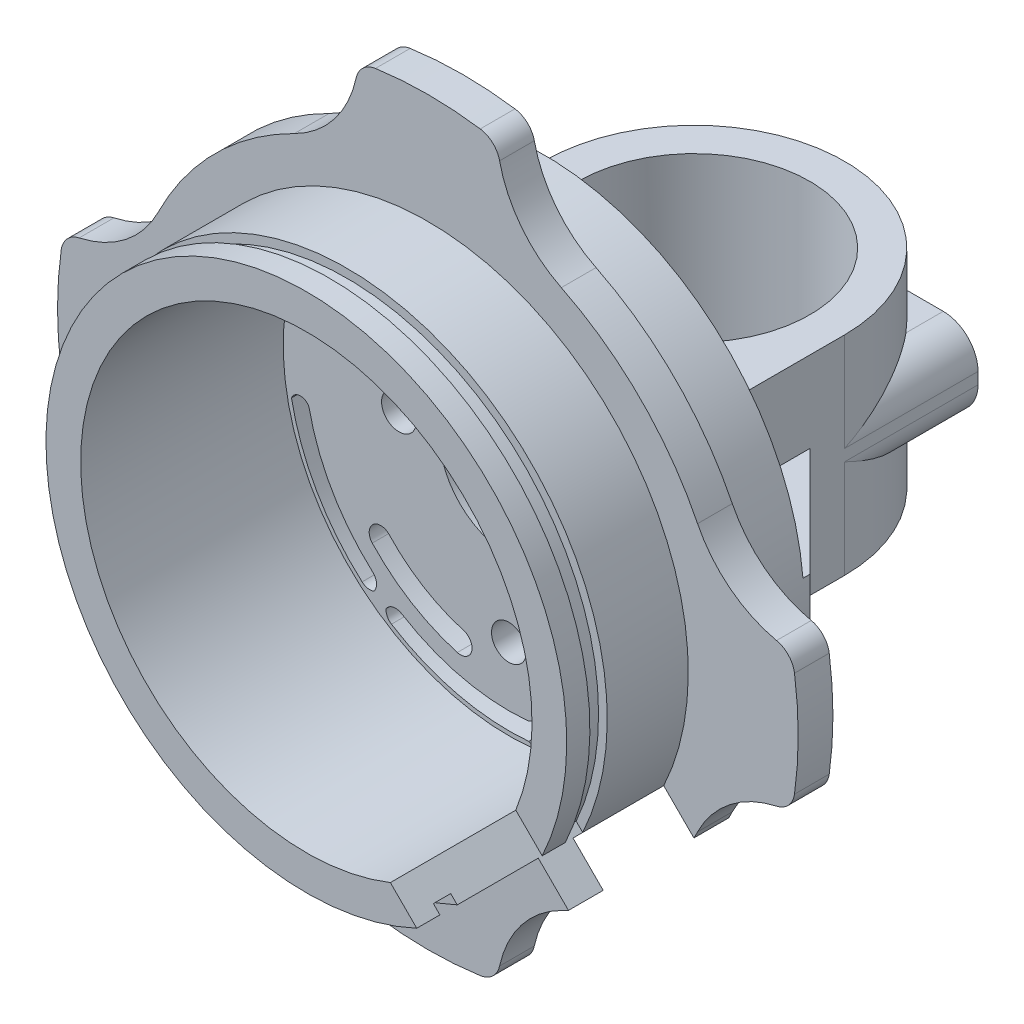
SolidWorks part; units mm, degrees
ref_plane "前视基准面" through (0, 0, 0) normal (0, 0, 1) x (1, 0, 0)
ref_plane "上视基准面" through (0, 0, 0) normal (0, 1, 0) x (1, 0, 0)
ref_plane "右视基准面" through (0, 0, 0) normal (1, 0, 0) x (0, 0, -1)
other "Configuration Table"
sketch "草图1" plane through (0, 0, 0) normal (0, 0, 1) x (1, 0, 0)
  circle A0 centre (0, 0) radius 18
  dimension "D1" = 36
extrude "凸台-拉伸1" add sketch "草图1" along normal blind 3
sketch "草图2" plane through (0, 0, 0) normal (0, 0, -1) x (-1, 0, 0)
  line L1 (13, -9) -> (-13, -9)
  line L2 (13, -9) -> (13, 9)
  line L3 (13, 9) -> (-13, 9)
  line L4 (-13, -9) -> (-13, 9)
  line L5 (13, -9) -> (-13, 9) construction
  line L6 (13, 9) -> (-13, -9) construction
  point P0 (0, 0)
  dimension "D1" = 26
  dimension "D2" = 18
extrude "凸台-拉伸2" add sketch "草图2" along normal blind 13
sketch "草图5" plane through (0, 0, 0) normal (0, 1, 0) x (1, 0, 0)
  line L0 (-13, 13) -> (13, 13)
  arc A0 (13, 13) -> (-13, 13) centre (0, 13) ccw
extrude "凸台-拉伸3" add sketch "草图5" along normal mid plane 18
sketch "草图6" plane through (0, 9, 0) normal (0, 1, 0) x (1, 0, 0)
  line L0 (-13, 13) -> (13, 13) construction
  circle A0 centre (0, 13) radius 10
  dimension "D1" = 20
extrude "切除-拉伸1" cut sketch "草图6" against normal through all
sketch "草图7" plane through (0, 0, 3) normal (0, 0, 1) x (1, 0, 0)
  line L0 (-10, 0) -> (10, 0) construction
  line L1 (-10, 9) -> (-10, -9) construction
  line L2 (10, -9) -> (10, 9) construction
  line L3 (0, 9) -> (0, -9) construction
  line L4 (-13, 9) -> (13, 9) construction
  line L5 (13, -9) -> (-13, -9) construction
  circle A0 centre (-9.5, 0) radius 1.5
  circle A1 centre (9.5, 0) radius 1.5
  circle A2 centre (0, 12.5) radius 1.5
  circle A3 centre (0, -12.5) radius 1.5
  dimension "D1" = 3
  dimension "D3" = 3
  dimension "D2" = 9.5
  dimension "D4" = 12.5
extrude "切除-拉伸2" cut sketch "草图7" against normal through all
sketch "草图8" plane through (0, 0, 0) normal (0, 1, 0) x (1, 0, 0)
  line L0 (0, 23) -> (0, 3) construction
  line L1 (-6, 24.5326) -> (-13, 24.5326)
  line L2 (-13, 24.5326) -> (-13, 13)
  line L5 (-11, 19.9283) -> (-11, -3) construction
  line L6 (6, 24.5326) -> (13, 24.5326)
  line L7 (13, 24.5326) -> (13, 13)
  arc A0 (-6, 24.5326) -> (-13, 13) centre (0, 13) ccw
  circle A2 centre (0, 13) radius 10 construction
  arc A3 (6, 24.5326) -> (13, 13) centre (0, 13) cw
  dimension "D1" = 7
  dimension "D2" = 2
extrude "凸台-拉伸4" add sketch "草图8" along normal mid plane 7
sketch "草图9" plane through (0, 0, -24.5326) normal (0, 0, -1) x (-1, 0, 0)
  circle A0 centre (9.5, 0) radius 1.5
  circle A1 centre (-9.5, 0) radius 1.5
extrude "切除-拉伸3" cut sketch "草图9" against normal through all
fillet "圆角1" radius 3 4 edges at (-13, -3.5, -18.7663) (-13, 3.5, -18.7663) (13, 3.5, -18.7663) (13, -3.5, -18.7663)
sketch "草图10" plane through (0, 0, 3) normal (0, 0, 1) x (1, 0, 0)
  circle A0 centre (0, 0) radius 6
extrude "切除-拉伸4" cut sketch "草图10" against normal blind 10
sketch "草图12" plane through (0, 0, 3) normal (0, 0, 1) x (1, 0, 0)
  circle A0 centre (0, 0) radius 18
  circle A1 centre (0, 0) radius 26
  dimension "D1" = 52
extrude "凸台-拉伸5" add sketch "草图12" against normal blind 3
sketch "草图13" plane through (0, 0, 3) normal (0, 0, 1) x (1, 0, 0)
  circle A0 centre (0, 0) radius 22.5
  circle A1 centre (0, 0) radius 19.5
  dimension "D1" = 45
  dimension "D2" = 39
extrude "凸台-拉伸6" add sketch "草图13" along normal blind 17.5
ref_plane "基准面2" through (0, 0, 18.5) normal (0, 0, 1) x (1, 0, 0)
sketch "草图21" plane through (0, 0, 18.5) normal (0, 0, 1) x (1, 0, 0)
  circle A0 centre (0, 0) radius 21.75
  circle A1 centre (0, 0) radius 22.5
  dimension "D1" = 43.5
extrude "切除-拉伸7" cut sketch "草图21" against normal blind 1.5
sketch "草图22" plane through (0, 0, 20.5) normal (0, 0, 1) x (1, 0, 0)
  line L0 (0, 0) -> (27.7403, -27.7403) construction
  line L1 (10.8378, 0) -> (0, -10.8378)
  line L2 (0, -10.8378) -> (13.8702, -24.7079)
  line L3 (13.8702, -24.7079) -> (24.7079, -13.8702)
  line L4 (10.8378, 0) -> (24.7079, -13.8702)
  point P8 (19.2891, -19.2891)
  point P9 (5.4189, -5.4189)
extrude "切除-拉伸8" cut sketch "草图22" against normal up to surface (17.5 mm away) up to face at (22.5, 0, 3)
sketch "草图25" plane through (0, 0, 3) normal (0, 0, 1) x (1, 0, 0)
  line L4 (7.2603, -18.098) -> (5.5811, -16.4189)
  line L5 (7.2603, -18.098) -> (14.4584, -25.2962)
  line L6 (18.098, -7.2603) -> (25.2962, -14.4584)
  line L7 (25.2962, -14.4584) -> (14.4584, -25.2962)
  line L8 (13, -9) -> (5.5811, -16.4189)
  line L9 (18.098, -7.2603) -> (16.4189, -5.5811)
  line L10 (13, -9) -> (16.4189, -5.5811)
extrude "切除-拉伸11" cut sketch "草图25" against normal blind 3
sketch "草图28" plane through (13, 0, 0) normal (1, 0, 0) x (0, 0, -1)
  line L0 (0, 2) -> (0, -2)
  line L1 (10, -2) -> (0, -2)
  line L2 (10, -2) -> (10, 2)
  line L3 (10, 2) -> (0, 2)
  line L5 (10, -2) -> (0, 0) construction
  line L6 (10, 2) -> (0, 0) construction
  point P0 (0, 0)
  dimension "D1" = 4
  dimension "D2" = 10
extrude "凸台-拉伸10" add sketch "草图28" along normal blind 10
sketch "草图29" plane through (0, 2, 0) normal (0, 1, 0) x (1, 0, 0)
  line L0 (13, 10) -> (23, 0)
  line L1 (23, 0) -> (23, 10)
  line L2 (23, 10) -> (13, 10)
extrude "切除-拉伸13" cut sketch "草图29" against normal blind 10
mirror "镜向1" about plane through (0, 0, 0) normal (1, 0, 0) of "切除-拉伸13", "凸台-拉伸10"
sketch "草图32" plane through (0, 0, 3) normal (0, 0, 1) x (1, 0, 0)
  line L0 (-17.8321, 4.0457) -> (17.8321, 4.0457) construction
  line L1 (-11.8006, 9.9792) -> (11.8006, 9.9792) construction
  line L2 (-1.25, 18.9898) -> (-1.25, 17.4863)
  line L3 (1.25, 18.9898) -> (1.25, 17.4863)
  line L4 (0, -25.575) -> (0, 25.575) construction
  line L5 (-1.25, 16.098) -> (-1.25, 14.7094)
  line L6 (1.25, 16.098) -> (1.25, 14.7094)
  arc A0 (-17.8321, 4.0457) -> (-1.25, 18.2425) centre (0, 0) cw construction
  arc A1 (18.6469, 3.8037) -> (1.25, 18.9898) centre (0, 0) ccw
  arc A2 (17.0074, 4.2519) -> (1.25, 17.4863) centre (0, 0) ccw
  arc A3 (17.0074, 4.2519) -> (18.6469, 3.8037) centre (17.8321, 4.0457) ccw
  arc A4 (-18.4627, 4.6157) -> (-17.0074, 4.2519) centre (-17.8321, 4.0457) ccw
  arc A5 (-11.8006, 9.9792) -> (-1.25, 15.4038) centre (0, 0) cw construction
  arc A6 (12.329, 10.4261) -> (1.25, 16.098) centre (0, 0) ccw
  arc A7 (11.2722, 9.5324) -> (1.25, 14.7094) centre (0, 0) ccw
  arc A8 (11.2722, 9.5324) -> (12.329, 10.4261) centre (11.8006, 9.9792) ccw
  arc A9 (-12.329, 10.4261) -> (-11.2722, 9.5324) centre (-11.8006, 9.9792) ccw
  arc A10 (-1.25, 18.9898) -> (-18.4627, 4.6157) centre (0, 0) ccw
  arc A11 (1.25, 18.2425) -> (17.8321, 4.0457) centre (0, 0) cw construction
  arc A12 (-1.25, 17.4863) -> (-17.0074, 4.2519) centre (0, 0) ccw
  arc A13 (-1.25, 16.098) -> (-12.329, 10.4261) centre (0, 0) ccw
  arc A14 (1.25, 15.4038) -> (11.8006, 9.9792) centre (0, 0) cw construction
  arc A15 (-1.25, 14.7094) -> (-11.2722, 9.5324) centre (0, 0) ccw
  point P4 (0, 18.3809)
  point P15 (0, 15.4544)
  dimension "D1" = 1.5
  dimension "D2" = 2.5
  dimension "D3" = 1.25
extrude "切除-拉伸16" cut sketch "草图32" against normal blind 10
sketch "草图33" plane through (0, 0, 3) normal (0, 0, 1) x (1, 0, 0)
  line L1 (-11.9807, -14.9106) -> (-11.0412, -13.7413)
  line L2 (-10.9114, -15.71) -> (-10.0558, -14.478)
  arc A0 (-18.0116, -3.8956) -> (-11.5426, -14.3653) centre (0, 0) ccw construction
  arc A1 (-18.7852, -3.6026) -> (-11.9807, -14.9106) centre (0, 0) ccw
  arc A2 (-17.2712, -3.5268) -> (-11.0412, -13.7413) centre (0, 0) ccw
  arc A3 (-17.2712, -3.5268) -> (-18.7852, -3.6026) centre (-18.0116, -3.8956) ccw
  arc A4 (1.7234, -19.0498) -> (1.7139, -17.544) centre (2.2211, -18.2937) ccw
  arc A5 (-11.0705, -10.297) -> (-4.1806, -14.5295) centre (0, 0) ccw construction
  arc A6 (-11.8027, -10.9781) -> (-4.4571, -15.4905) centre (0, 0) ccw
  arc A7 (-10.3382, -9.616) -> (-3.9041, -13.5685) centre (0, 0) ccw
  arc A8 (-10.3382, -9.616) -> (-11.8027, -10.9781) centre (-11.0705, -10.297) ccw
  arc A9 (-4.4571, -15.4905) -> (-3.9041, -13.5685) centre (-4.1806, -14.5295) ccw
  arc A10 (-10.0558, -14.478) -> (1.7139, -17.544) centre (0, 0) ccw
  arc A11 (-10.5124, -15.1355) -> (2.2211, -18.2937) centre (0, 0) ccw construction
  arc A12 (-10.9114, -15.71) -> (1.7234, -19.0498) centre (0, 0) ccw
  point P4 (-11.0639, -14.799)
  point P13 (-7.9137, -12.8824)
  dimension "D1" = 1.5
  dimension "D2" = 2
  dimension "D3" = 4
extrude "切除-拉伸17" cut sketch "草图33" against normal blind 10
fillet "圆角4" radius 1 6 edges at (-11.0412, -13.7413, 1.5) (-10.0558, -14.478, 1.5) (1.25, 17.4863, 1.5) (-1.25, 17.4863, 1.5) (-1.25, 14.7094, 1.5) (1.25, 14.7094, 1.5)
fillet "圆角5" radius 1 6 edges at (-1.25, 18.9898, 1.5) (1.25, 18.9898, 1.5) (1.25, 16.098, 1.5) (-1.25, 16.098, 1.5) (-10.9114, -15.71, 1.5) (-11.9807, -14.9106, 1.5)
fillet "圆角6" radius 1 2 edges at (16.4189, -5.5811, 1.5) (5.5811, -16.4189, 1.5)
fillet "圆角7" radius 1 2 edges at (22.9869, -12.1491, 1.5) (12.1491, -22.9869, 1.5)
sketch "草图35" plane through (0, 0, 3) normal (0, 0, 1) x (1, 0, 0)
  circle A0 centre (0, 0) radius 22.5
  circle A1 centre (0, 0) radius 26
extrude "切除-拉伸18" cut sketch "草图35" against normal blind 10
ref_plane "基准面3" through (0, 0, 10) normal (0, 0, 1) x (1, 0, 0)
sketch "草图36" plane through (0, 0, 10) normal (0, 0, 1) x (1, 0, 0)
  circle A0 centre (0, 0) radius 22.5
  circle A1 centre (0, 0) radius 26
  dimension "D1" = 3.5
extrude "凸台-拉伸11" add sketch "草图36" against normal blind 3
sketch "草图37" plane through (0, 0, 10) normal (0, 0, 1) x (1, 0, 0)
  line L0 (9.5397, -20.3775) -> (20.3775, -9.5397)
  line L1 (20.3775, -9.5397) -> (25.7964, -14.9586)
  line L2 (25.7964, -14.9586) -> (13.5661, -24.4039)
  line L3 (13.5661, -24.4039) -> (9.5397, -20.3775)
extrude "切除-拉伸19" cut sketch "草图37" against normal blind 3
sketch "草图38" plane through (0, 0, 10) normal (0, 0, 1) x (1, 0, 0)
  line L0 (6, 25.2982) -> (6, 31.4325)
  line L2 (6, -31.4325) -> (6, -25.2982)
  line L4 (-6, -31.4325) -> (-6, -25.2982)
  line L5 (5.0499, -31.599) -> (4.103, -25.6742) construction
  line L6 (5.0499, 31.599) -> (4.103, 25.6742) construction
  line L7 (-4.103, -25.6742) -> (-5.0499, -31.599) construction
  line L8 (-4.103, 25.6742) -> (-5.0499, 31.599) construction
  line L9 (-6, 25.2982) -> (-6, 31.4325)
  arc A0 (-6, -31.4325) -> (6, -31.4325) centre (0, 0) ccw
  arc A1 (6, 31.4325) -> (-6, 31.4325) centre (0, 0) ccw
  arc A2 (-6, -25.2982) -> (6, -25.2982) centre (0, 0) ccw
  arc A3 (6, 25.2982) -> (-6, 25.2982) centre (0, 0) ccw
  dimension "D1" = 64
extrude "凸台-拉伸12" add sketch "草图38" against normal blind 3
fillet "圆角8" radius 10 4 edges at (-6, -25.2982, 8.5) (6, -25.2982, 8.5) (6, 25.2982, 8.5) (-6, 25.2982, 8.5)
fillet "圆角9" radius 2 4 edges at (6, -31.4325, 8.5) (-6, -31.4325, 8.5) (-6, 31.4325, 8.5) (6, 31.4325, 8.5)
sketch "草图39" plane through (0, 0, 10) normal (0, 0, 1) x (1, 0, 0)
  line L0 (-25.2982, 6) -> (-31.4325, 6)
  line L1 (31.4325, -6) -> (25.2982, -6)
  line L3 (31.4325, 6) -> (25.2982, 6)
  line L5 (31.5301, -5.4639) -> (25.6182, -4.4394) construction
  line L6 (31.5301, 5.4639) -> (25.6182, 4.4394) construction
  line L7 (-25.6182, 4.4394) -> (-31.5301, 5.4639) construction
  line L8 (-25.6182, -4.4394) -> (-31.5301, -5.4639) construction
  line L9 (-25.2982, -6) -> (-31.4325, -6)
  arc A0 (-31.4325, 6) -> (-31.4325, -6) centre (0, 0) ccw
  arc A1 (-25.2982, 6) -> (-25.2982, -6) centre (0, 0) ccw
  arc A2 (31.4325, -6) -> (31.4325, 6) centre (0, 0) ccw
  arc A3 (25.2982, -6) -> (25.2982, 6) centre (0, 0) ccw
  point P0 (0, 0)
  dimension "D2" = 64
extrude "凸台-拉伸13" add sketch "草图39" against normal blind 3
fillet "圆角10" radius 10 4 edges at (-25.2982, 6, 8.5) (-25.2982, -6, 8.5) (25.2982, 6, 8.5) (25.2982, -6, 8.5)
fillet "圆角11" radius 2 4 edges at (31.4325, 6, 8.5) (31.4325, -6, 8.5) (-31.4325, -6, 8.5) (-31.4325, 6, 8.5)
